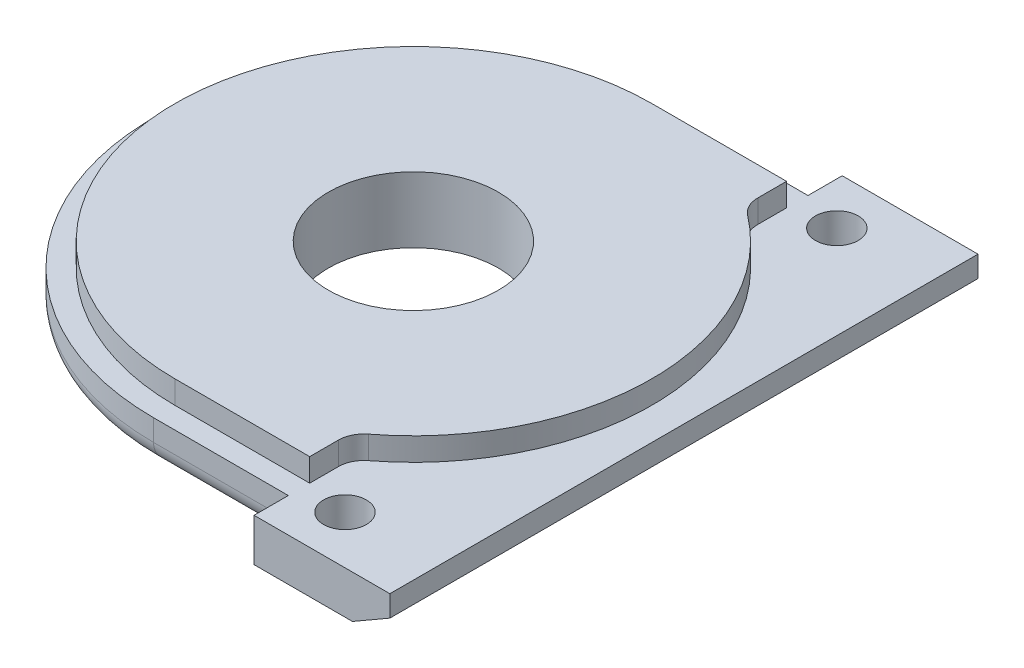
SolidWorks part; units mm, degrees
material "6061-T6 (SS)"
ref_plane "Front Plane" through (0, 0, 0) normal (0, 0, 1) x (1, 0, 0)
ref_plane "Top Plane" through (0, 0, 0) normal (0, 1, 0) x (1, 0, 0)
ref_plane "Right Plane" through (0, 0, 0) normal (1, 0, 0) x (0, 0, -1)
sketch "Sketch1" plane through (0, 0, 0) normal (0, 1, 0) x (1, 0, 0)
  line L0 (-13.2912, 20.8898) -> (-0.69, 20.8898)
  line L2 (-0.69, 24.0921) -> (-0.69, 20.8898)
  line L4 (12.01, 24.0921) -> (12.01, -26.9079)
  line L5 (-13.2912, -23.7056) -> (-0.69, -23.7056)
  line L6 (-0.69, -23.7056) -> (-0.69, -26.9079)
  line L13 (-0.69, -28.9079) -> (-0.69, -26.9079)
  line L15 (12.01, -28.9079) -> (12.01, -26.9079)
  line L16 (12.01, -28.9079) -> (-0.69, -28.9079)
  line L18 (12.01, 26.0921) -> (12.01, 24.0921)
  line L20 (-0.69, 26.0921) -> (-0.69, 24.0921)
  line L21 (-0.69, 26.0921) -> (12.01, 26.0921)
  arc A0 (-13.2912, 20.8898) -> (-13.2912, -23.7056) centre (-13.2912, -1.4079) ccw
extrude "Boss-Extrude1" add sketch "Sketch1" along normal blind 4
sketch "Sketch2" plane through (0, 4, 0) normal (0, 1, 0) x (1, 0, 0)
  line L0 (-0.69, 20.8898) -> (-0.69, 16.9877)
  line L1 (-0.69, -23.7056) -> (-0.69, -19.8035)
  line L2 (-0.69, -23.7056) -> (-13.2912, -23.7056)
  line L3 (-0.69, 20.8898) -> (-13.2912, 20.8898)
  arc A0 (-0.69, -19.8035) -> (-0.69, 16.9877) centre (-13.2912, -1.4079) ccw
  arc A1 (-13.2912, 20.8898) -> (-13.2912, -23.7056) centre (-13.2912, -1.4079) ccw
extrude "Boss-Extrude2" add sketch "Sketch2" along normal blind 2.25
sketch "Sketch3" plane through (0, 0, 0) normal (0, -1, 0) x (1, 0, 0)
  circle A0 centre (-13.2912, 1.4079) radius 7.95
  dimension "D1" = 15.9
extrude "Cut-Extrude1" cut sketch "Sketch3" against normal blind 9.25
sketch "Sketch4" plane through (0, 0, 0) normal (0, -1, 0) x (1, 0, 0)
  line L0 (-0.69, -26.0921) -> (3.31, -26.0921) construction
  line L1 (12.01, -26.0921) -> (-0.69, -26.0921) construction
  line L3 (3.31, -26.0921) -> (3.31, -21.5921) construction
  line L4 (-0.69, 28.9079) -> (3.31, 28.9079) construction
  line L5 (3.31, 28.9079) -> (3.31, 24.4079) construction
  circle A2 centre (3.31, -21.5921) radius 2
  circle A3 centre (3.31, 24.4079) radius 2
extrude "Cut-Extrude2" cut sketch "Sketch4" against normal blind 9.25
sketch "Sketch5" plane through (0, 0, 0) normal (0, -1, 0) x (1, 0, 0)
  line L9 (-20.9172, 10.6082) -> (-24.2357, 16.3644)
  line L12 (-17.4459, 12.6124) -> (-20.7716, 18.3644)
  line L14 (-1.5104, 3.4121) -> (5.1338, 3.4079)
  line L17 (-1.5104, -0.5963) -> (5.1338, -0.5921)
  line L19 (-17.4459, -9.7966) -> (-20.7716, -15.5486)
  line L22 (-20.9172, -7.7924) -> (-24.2357, -13.5486)
  circle A2 centre (-13.2912, 1.4079) radius 11.95
  arc A3 (-1.5104, 3.4121) -> (-17.4459, 12.6124) centre (-13.2912, 1.4079) ccw
  circle A4 centre (-13.2912, 1.4079) radius 18.45
  circle A5 centre (-13.2912, 1.4079) radius 18.45
  circle A6 centre (-13.2912, 1.4079) radius 18.45
  circle A7 centre (-13.2912, 1.4079) radius 18.45
  arc A8 (-20.9172, 10.6082) -> (-20.9172, -7.7924) centre (-13.2912, 1.4079) ccw
  arc A9 (-17.4459, -9.7966) -> (-1.5104, -0.5963) centre (-13.2912, 1.4079) ccw
  point P14 (-13.2912, 1.4079)
  dimension "D1" = 4
  dimension "D2" = 10.5
  dimension "D3" = 3
extrude "Cut-Extrude3" cut sketch "Sketch5" against normal blind 3 contours A8 L9 A4 L22 | L14 A4 L12 A3 | A9 L19 A4 L17 region at (-26.6764, 0, 1.4079) region at (-6.5986, 0, 12.9998) region at (-6.5986, 0, -10.184)
fillet "Fillet1" radius 2.36 12 edges at (5.0501, 1.5, 3.4079) (-1.5104, 1.5, 3.4121) (5.0501, 1.5, -0.5922) (-24.1939, 1.5, 16.2919) (-20.7297, 1.5, 18.2919) (-1.5104, 1.5, -0.5963) (-20.7297, 1.5, -15.4761) (-20.9172, 1.5, 10.6082) (-20.9172, 1.5, -7.7924) (-24.1939, 1.5, -13.4761) (-17.4459, 1.5, -9.7966) (-17.4459, 1.5, 12.6124)
chamfer "Chamfer1" distance 3.5 angle 30 1 edges at (12.01, 0, 1.4079) first distance on face at (-7.8304, 0, -8.0504)
sketch "Sketch6" plane through (0, 0, 0) normal (0, -1, 0) x (1, 0, 0)
  line L2 (-0.69, -22.8898) -> (-13.2912, -22.8898)
  line L3 (-13.2912, 25.7056) -> (-0.69, 25.7056)
  line L4 (-0.69, -20.8898) -> (-13.2912, -20.8898)
  line L5 (-13.2912, 23.7056) -> (-0.69, 23.7056)
  line L6 (-0.69, -20.8898) -> (-13.2912, -20.8898)
  line L7 (-13.2912, 23.7056) -> (-0.69, 23.7056)
  line L8 (-0.69, 25.7056) -> (-0.69, 23.7056)
  line L9 (-0.69, -20.8898) -> (-0.69, -22.8898)
  arc A1 (-13.2912, 25.7056) -> (-13.2912, -22.8898) centre (-13.2912, 1.4079) ccw
  arc A2 (-13.2912, 23.7056) -> (-13.2912, -20.8898) centre (-13.2912, 1.4079) ccw
  arc A3 (-13.2912, 23.7056) -> (-13.2912, -20.8898) centre (-13.2912, 1.4079) ccw
  dimension "D1" = 0
  dimension "D2" = 2
extrude "Boss-Extrude3" add sketch "Sketch6" against normal blind 4
fillet "Fillet2" radius 2 3 edges at (-6.9906, 0, 25.7056) (-6.9906, 0, -22.8898) (-37.5889, 0, 1.4079)
ref_axis "Axis2" through (-13.2912, 6.25, 1.4079) along (0, -1, 0)
sketch "Sketch7" plane through (0, 6.25, 0) normal (0, 1, 0) x (1, 0, 0)
  line L1 (-41.0707, -28.482) -> (15.4918, -28.482)
  line L2 (-41.0707, -28.482) -> (-41.0707, 23.4819)
  line L3 (-41.0707, 23.4819) -> (15.4918, 23.4819)
  line L4 (15.4918, -28.482) -> (15.4918, 23.4819)
extrude "Cut-Extrude4" cut sketch "Sketch7" against normal blind 0.1
fillet "Fillet3" radius 2.38 2 edges at (-0.69, 5.075, -16.9877) (-0.69, 5.075, 19.8035)
